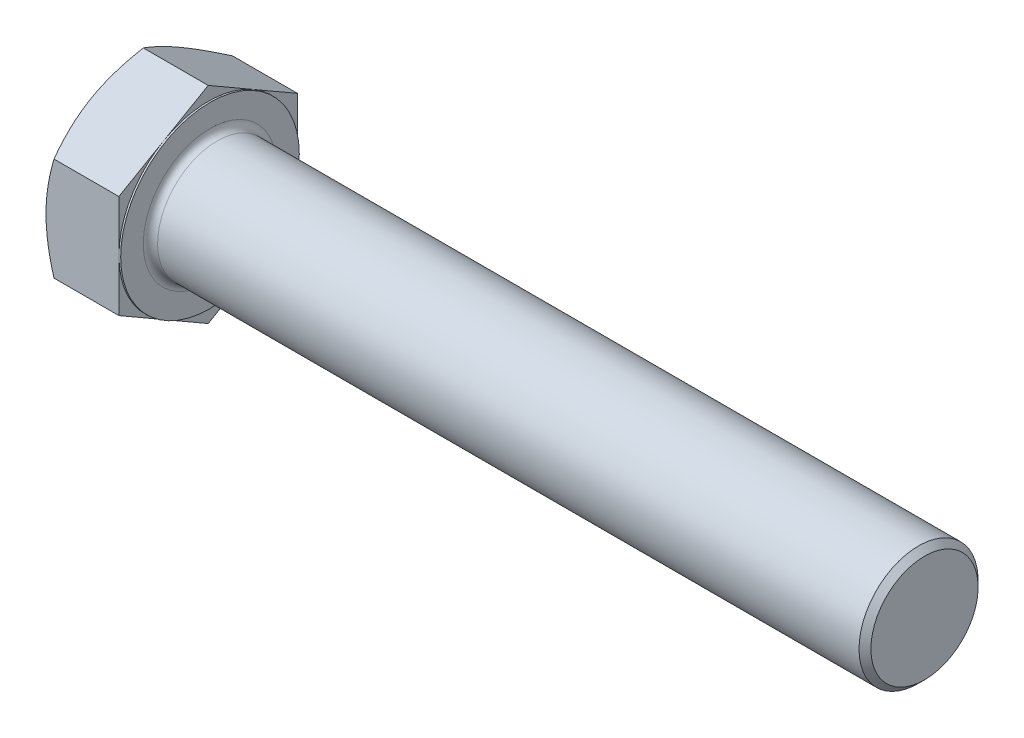
SolidWorks part; units mm, degrees
extrude "BaseHead" add sketch "Sketch1" along normal blind 15.9258
sketch "Sketch1" plane through (0, 0, 0) normal (1, 0, 0) x (0, 0, -1)
  line L0 (19.05, 10.9985) -> (19.05, -10.9985)
  line L1 (-19.05, 10.9985) -> (-19.05, -10.9985)
  line L2 (19.05, -10.9985) -> (0, -21.997)
  line L3 (0, -21.997) -> (-19.05, -10.9985)
  line L4 (19.05, 10.9985) -> (0, 21.997)
  line L5 (0, 21.997) -> (-19.05, 10.9985)
  dimension "D2" = 120
  dimension "D3" = 19.05
  dimension "D4" = 19.05
  dimension "D5" = 19.05
revolve "HeadChamfer" cut sketch "Sketch3" angle 360 about L6 other way angle 60
sketch "Sketch3" plane through (0, 0, 0) normal (0, 0, 1) x (1, 0, 0)
  line L0 (0, 19.05) -> (5.3677, 28.347)
  line L1 (0, 21.997) -> (0, 10.9985) construction
  line L2 (5.3677, 28.347) -> (5.3677, 34.697)
  line L3 (5.3677, 34.697) -> (-12.7, 34.697)
  line L4 (-12.7, 34.697) -> (-12.7, 19.05)
  line L5 (-12.7, 19.05) -> (0, 19.05)
  line L6 (0, 0) -> (99.06, 0) construction
  line L7 (15.9258, 21.997) -> (0, 21.997) construction
  dimension "D1" = 19.05
  dimension "D2" = 6.35
  dimension "D3" = 12.7
  dimension "D4" = 6.35
  dimension "Head_ch_ang" = 30
ref_plane "Plane1" through (0, 0, 0) normal (0, 0, 1) x (1, 0, 0)
ref_plane "Plane2" through (0, 0, 0) normal (0, 1, 0) x (1, 0, 0)
ref_plane "Plane3" through (0, 0, 0) normal (1, 0, 0) x (0, 0, -1)
sketch "BodySke" plane through (0, 0, 0) normal (0, 0, 1) x (1, 0, 0)
  line L0 (0, 10.9985) -> (0, -10.9985) construction
  line L1 (0, 0) -> (168.3258, 0)
  line L2 (0, 0) -> (0, 12.7)
  line L3 (0, 12.7) -> (167.0571, 12.7)
  line L4 (168.3258, 0) -> (168.3258, 11.4313)
  line L5 (15.9258, 21.997) -> (15.9258, 10.9985) construction
  line L6 (168.3258, 11.4313) -> (167.0571, 12.7)
  line L7 (0, 0) -> (96.52, 0) construction
  line L8 (168.3258, -11.4313) -> (167.0571, -12.7) construction
  line L9 (0, -12.7) -> (167.0571, -12.7) construction
  line L10 (18.0416, 15.24) -> (18.0416, -1.27) construction
  line L11 (15.9258, 15.24) -> (15.9258, -1.27) construction
  line L12 (15.9258, 10.9985) -> (15.9258, -10.9985) construction
  dimension "Diameter" = 25.4
revolve "BaseBody" add sketch "BodySke" angle 360 about L7
cosmetic thread "ThreadCosmetic" [suppressed] parameters "Thread_length"=150.2842, "Thread_minor"=22.8625
sketch "Sketch4" plane through (0, 0, 0) normal (0, 0, 1) x (1, 0, 0)
  line L1 (15.9258, 21.997) -> (15.9258, 10.9985) construction
  line L2 (15.9258, 19.05) -> (15.5448, 19.05)
  line L3 (15.9258, 19.05) -> (15.9258, 47.397)
  line L4 (15.9258, 47.397) -> (15.5448, 47.397)
  line L5 (0, 0) -> (95.25, 0) construction
  line L6 (0, 0) -> (96.52, 0) construction
  line L7 (15.5448, 19.05) -> (15.5448, 47.397)
  line L8 (15.9258, 21.997) -> (1.7015, 21.997) construction
  dimension "D1" = 19.05
  dimension "D2" = 25.4
revolve "BearingFace" cut sketch "Sketch4" angle 360 about L5
fillet "HeadFillet" radius 1.524 1 edges at (15.9258, 0, -12.7)
sketch "ThdSchSke" plane through (0, 0, 0) normal (0, 0, 1) x (1, 0, 0)
  line L0 (18.0416, -11.4313) -> (17.1532, -12.7)
  line L1 (18.0416, -11.4313) -> (18.93, -12.7)
  line L2 (18.93, -12.7) -> (18.93, -15.875)
  line L3 (-3.175, 0) -> (5.1513, 0) construction
  line L5 (18.93, -15.875) -> (17.1532, -15.875)
  line L6 (17.1532, -15.875) -> (17.1532, -12.7)
  dimension "Thread_minor" = 22.8625
  dimension "Diameter" = 25.4
  dimension "Start" = 18.0416
revolve "ThreadSchematic" [suppressed] cut sketch "ThdSchSke" angle 360 about L3
pattern_linear "ThdSchPat" [suppressed]
equation "\"D3@Sketch1\" = \"Width_flats@Sketch1\" / 2"
equation "\"D4@Sketch1\" = \"D3@Sketch1\""
equation "\"D5@Sketch1\" = \"D4@Sketch1\""
equation "\"Thread_minor@ThreadCosmetic\" = \"Minor_dia@BodySke\""
equation "\"D1@Sketch3\" = \"Width_flats@Sketch1\" / 2"
equation "\"D1@Sketch4\" = \"Width_flats@Sketch1\" / 2"
equation "\"Thread_length@ThreadCosmetic\" = ((sgn( (\"Length@BodySke\" - \"Advance@BodySke\" ) - \"Thread_nom@BodySke\" )-1)*( (\"Length@BodySke\" - \"Advance@BodySke\" ) - \"Thread_nom@BodySke\" ))/-2+ \"Thread_nom@BodySke\""
equation "\"Thread_minor@ThdSchSke\" = \"Minor_dia@BodySke\""
equation "\"Diameter@ThdSchSke\" = \"Diameter@BodySke\""
equation "\"Overcut@ThdSchSke\" = \"Diameter@BodySke\" * 1.25"
equation "\"Start@ThdSchSke\" = \"Head_ht@BaseHead\" + \"Length@BodySke\" - \"Thread_length@ThreadCosmetic\"  '---Non-countersunk---"
equation "\"Num_threads@ThdSchPat\" = int( \"Thread_length@ThreadCosmetic\" / \"Advance@BodySke\" + 0.999 )  + 1"
equation "\"Advance@ThdSchPat\" = \"Thread_length@ThreadCosmetic\" /  (\"Num_threads@ThdSchPat\" - 1) 'relax it"
equation "\"Num_threads@ThdSchPat\" = \"Num_threads@ThdSchPat\" - sgn( \"Num_threads@ThdSchPat\" - 1) '---chamfered tips only---"
